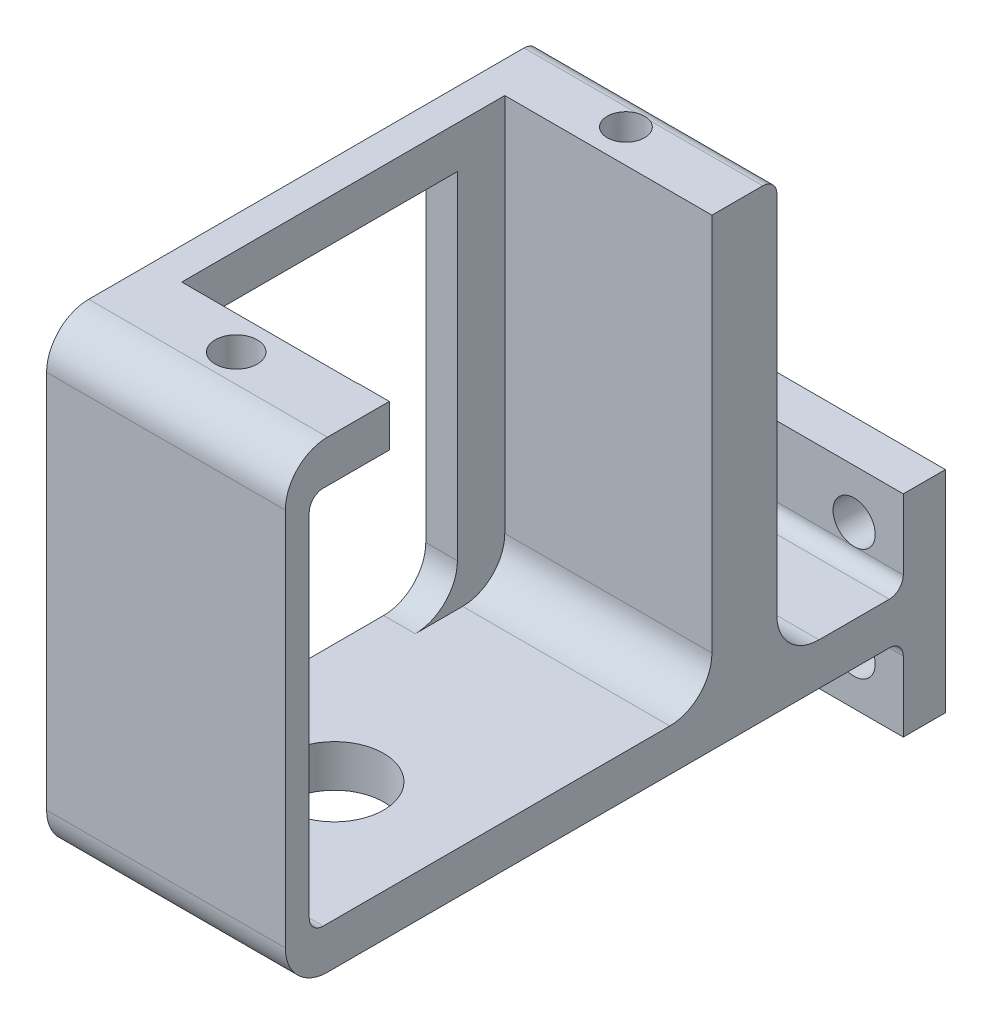
SolidWorks part; units mm, degrees
ref_plane "Front Plane" through (0, 0, 0) normal (0, 0, 1) x (1, 0, 0)
ref_plane "Top Plane" through (0, 0, 0) normal (0, 1, 0) x (1, 0, 0)
ref_plane "Right Plane" through (0, 0, 0) normal (1, 0, 0) x (0, 0, -1)
sketch "Sketch1" plane through (0, 0, 0) normal (0, 1, 0) x (1, 0, 0)
  line L0 (5.7626, -25.8648) -> (5.7626, 21.1352) construction
  line L1 (-2.7374, 21.1352) -> (14.2626, 21.1352)
  line L2 (-2.7374, 21.1352) -> (-2.7374, -25.8648)
  line L3 (-2.7374, -25.8648) -> (14.2626, -25.8648)
  line L4 (14.2626, 21.1352) -> (14.2626, -25.8648)
  circle A0 centre (5.7626, -13.8648) radius 3.5
  dimension "D2" = 35
  dimension "D3" = 7
  dimension "D5" = 0
  dimension "D1" = 47
  dimension "D4" = 17
extrude "Boss-Extrude1" add sketch "Sketch1" along normal blind 3
sketch "Sketch2" plane through (0, 3, 0) normal (0, 1, 0) x (1, 0, 0)
  line L0 (5.7626, -3.8648) -> (5.7626, 1.1352) construction
  line L1 (-2.7374, 21.1352) -> (-2.7374, -25.8648) construction
  line L2 (-2.7374, 1.1352) -> (14.2626, 1.1352)
  line L3 (-2.7374, 1.1352) -> (-2.7374, 9.1352)
  line L4 (-2.7374, 9.1352) -> (14.2626, 9.1352)
  line L5 (14.2626, 1.1352) -> (14.2626, 9.1352)
  line L6 (14.2626, -25.8648) -> (14.2626, 21.1352) construction
  line L8 (-2.7374, -25.8648) -> (14.2626, -25.8648)
  line L9 (-2.7374, -25.8648) -> (-2.7374, -24.1648)
  line L10 (-2.7374, -24.1648) -> (14.2626, -24.1648)
  line L11 (14.2626, -25.8648) -> (14.2626, -24.1648)
  circle A0 centre (5.7626, -13.8648) radius 10 construction
  dimension "D1" = 20
  dimension "D2" = 5
  dimension "D3" = 8
  dimension "D4" = 1.7
extrude "Boss-Extrude2" add sketch "Sketch2" along normal blind 27
sketch "Sketch3" plane through (0, 30, 0) normal (0, 1, 0) x (1, 0, 0)
  line L1 (-2.7374, 9.1352) -> (14.2626, 9.1352)
  line L2 (-2.7374, 9.1352) -> (-2.7374, -25.8648)
  line L3 (-2.7374, -25.8648) -> (14.2626, -25.8648)
  line L4 (14.2626, 9.1352) -> (14.2626, -25.8648)
extrude "Boss-Extrude3" add sketch "Sketch3" along normal blind 3
sketch "Sketch4" plane through (0, 30, 0) normal (0, -1, 0) x (1, 0, 0)
  circle A0 centre (5.7626, 13.8648) radius 3.5
extrude "Cut-Extrude1" cut sketch "Sketch4" against normal blind 3
sketch "Sketch5" plane through (0, 33, 0) normal (0, 1, 0) x (1, 0, 0)
  circle A0 centre (5.7626, -20.8648) radius 1.5
  circle A1 centre (5.7626, -13.8648) radius 3.5 construction
  circle A2 centre (5.7626, 6.8852) radius 1.331
  dimension "D1" = 7
  dimension "D2" = 3
  dimension "D3" = 27.75
extrude "Cut-Extrude2" cut sketch "Sketch5" against normal blind 15
sketch "Sketch7" plane through (0, 33, 0) normal (0, 1, 0) x (1, 0, 0)
  line L0 (5.7626, 4.5102) -> (5.7626, -18.4898) construction
  line L1 (-0.4874, 4.5102) -> (12.0126, 4.5102)
  line L2 (-0.4874, 4.5102) -> (-0.4874, -18.4898)
  line L3 (-0.4874, -18.4898) -> (12.0126, -18.4898)
  line L4 (12.0126, 4.5102) -> (12.0126, -18.4898)
  circle A0 centre (5.7626, -13.8648) radius 3.5 construction
  circle A1 centre (5.7626, 6.8852) radius 1.331 construction
  circle A2 centre (5.7626, -20.8648) radius 1.5 construction
  dimension "D4" = 2.375
  dimension "D1" = 12.5
  dimension "D2" = 23
  dimension "D3" = 0
  dimension "D5" = 2.375
extrude "Cut-Extrude3" cut sketch "Sketch7" against normal blind 30
sketch "Sketch8" plane through (0, 0, -21.1352) normal (0, 0, -1) x (-1, 0, 0)
  line L0 (2.7374, 3) -> (2.7374, 0) construction
  line L1 (-14.2626, -6) -> (2.7374, -6)
  line L2 (-14.2626, -6) -> (-14.2626, 9)
  line L3 (-14.2626, 9) -> (2.7374, 9)
  line L4 (2.7374, -6) -> (2.7374, 9)
  line L5 (-14.2626, 3) -> (-14.2626, 0) construction
  line L6 (-14.2626, 0) -> (2.7374, 0) construction
  line L7 (-14.2626, 3) -> (2.7374, 3) construction
  circle A0 centre (-10.7626, 5.5) radius 1.5
  circle A1 centre (-0.7626, 5.5) radius 1.5
  circle A2 centre (-10.7626, -2.5) radius 1.5
  circle A3 centre (-0.7626, -2.5) radius 1.5
  dimension "D5" = 3.5
  dimension "D6" = 3.5
  dimension "D7" = 3
  dimension "D8" = 3.5
  dimension "D9" = 3.5
  dimension "D10" = 3
  dimension "D11" = 3.5
  dimension "D12" = 3.5
  dimension "D13" = 3
  dimension "D14" = 3.5
  dimension "D15" = 3.5
  dimension "D16" = 3
  dimension "D1" = 0
  dimension "D2" = 0
  dimension "D3" = 6
  dimension "D4" = 6
  dimension "D17" = 17
  dimension "D18" = 15
extrude "Boss-Extrude4" add sketch "Sketch8" against normal blind 3
sketch "Sketch9" plane through (0, 33, 0) normal (0, 1, 0) x (1, 0, 0)
  line L0 (14.2626, -25.8648) -> (14.2626, 9.1352) construction
  line L1 (12.0126, 4.5102) -> (14.2626, 4.5102)
  line L2 (12.0126, 4.5102) -> (12.0126, -18.4624)
  line L3 (12.0126, -18.4624) -> (14.2626, -18.4624)
  line L4 (14.2626, 4.5102) -> (14.2626, -18.4624)
extrude "Cut-Extrude4" cut sketch "Sketch9" against normal blind 30
fillet "Fillet8" radius 3 1 edges at (5.7626, 0, 25.8648)
fillet "Fillet9" radius 3 1 edges at (5.7626, 33, 25.8648)
fillet "Fillet10" radius 3 1 edges
fillet "Fillet11" radius 3 1 edges at (6.8876, 3, -4.5102)
fillet "Fillet12" radius 3 1 edges
fillet "Fillet13" radius 1 1 edges at (5.7626, 3, -18.1352)
fillet "Fillet14" radius 1 1 edges at (5.7626, 0, -18.1352)
fillet "Fillet15" radius 1 1 edges at (5.7626, 3, 24.1648)
fillet "Fillet16" radius 1 1 edges at (5.7626, 30, 24.1648)
fillet "Fillet17" radius 1 1 edges at (5.7626, 33, -9.1352)
